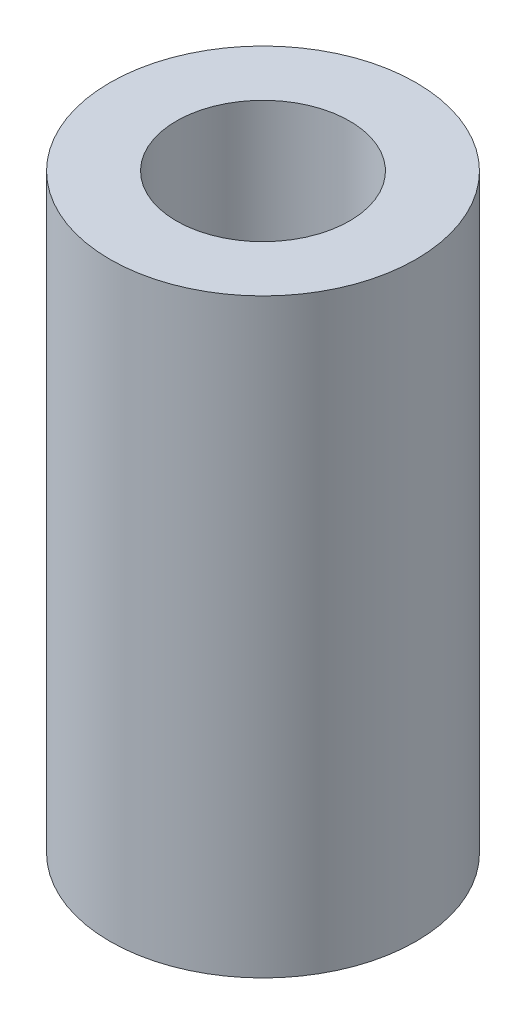
SolidWorks part; units mm, degrees
ref_plane "Front Plane" through (0, 0, 0) normal (0, 0, 1) x (1, 0, 0)
ref_plane "Top Plane" through (0, 0, 0) normal (0, 1, 0) x (1, 0, 0)
ref_plane "Right Plane" through (0, 0, 0) normal (1, 0, 0) x (0, 0, -1)
sketch "Sketch1" plane through (0, 0, 0) normal (0, 1, 0) x (1, 0, 0)
  circle A0 centre (0, 0) radius 12.5
  dimension "SLEEVE_OD" = 25
extrude "Boss-Extrude1" add sketch "Sketch1" along normal blind 48.2365
sketch "Sketch2" plane through (0, 0, 0) normal (0, 1, 0) x (1, 0, 0)
  circle A0 centre (0, 0) radius 7.0739
  dimension "BORE_D" = 14.1479
extrude "Cut-Extrude1" cut sketch "Sketch2" along normal through all
chamfer "Chamfer1" distance 2.4939 angle 66.891 rebuild error yes
